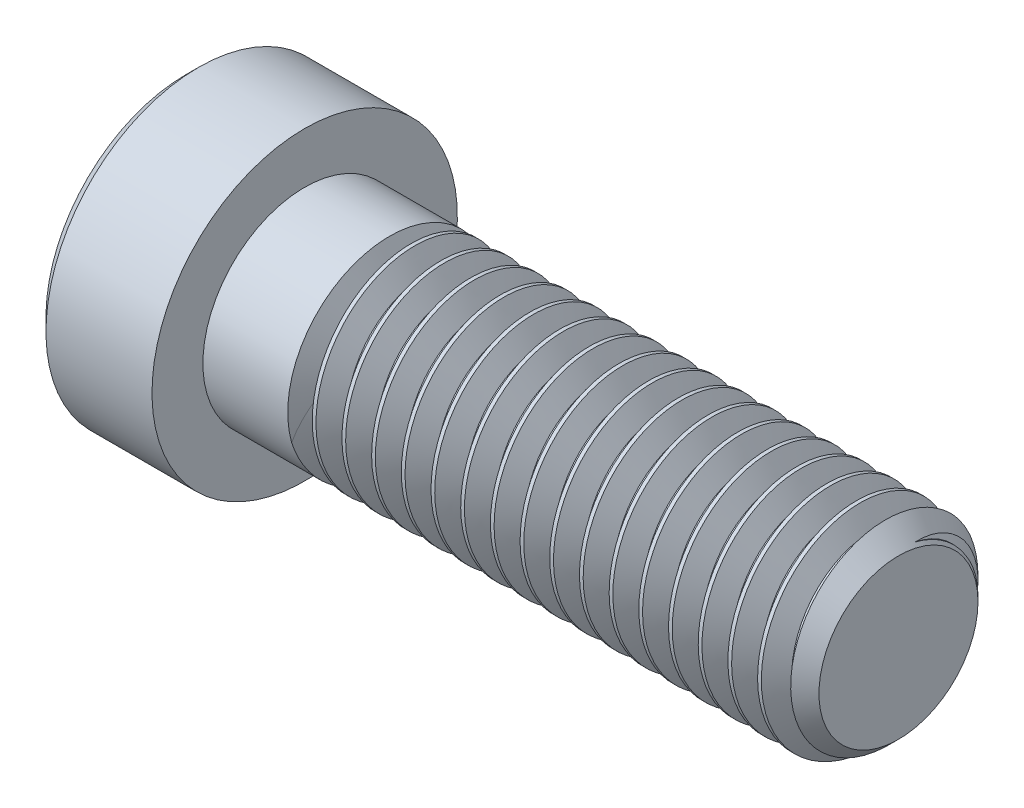
SolidWorks part; units mm, degrees
ref_plane "Front Plane" through (0, 0, 0) normal (0, 0, 1) x (1, 0, 0)
ref_plane "Top Plane" through (0, 0, 0) normal (0, 1, 0) x (1, 0, 0)
ref_plane "Right Plane" through (0, 0, 0) normal (1, 0, 0) x (0, 0, -1)
sketch "Sketch1" plane through (0, 0, 0) normal (0, 0, 1) x (1, 0, 0)
  line L0 (17.5, 0) -> (-17.5, 0) construction
  line L1 (17.5, 6) -> (17.5, -6) construction
  line L2 (-17.5, 9) -> (-17.5, -9) construction
  line L3 (-17.5, 9) -> (-23.75, 9) construction
  line L4 (-23.75, 9) -> (-24.5, 8.25) construction
  line L5 (-24.5, 8.25) -> (-24.5, -8.25) construction
  line L6 (-24.5, -8.25) -> (-23.75, -9) construction
  line L7 (-23.75, -9) -> (-17.5, -9) construction
  point P7 (-21, 0)
  point P12 (10.5, -6)
  dimension "D1" = 45
  dimension "Dec." = 12
  dimension "Length" = 35
  dimension "Head Dia" = 18
  dimension "Head Height" = 7
  dimension "Chamfer" = 0.75
  dimension "D2" = 7
  dimension "D3" = 3.5
ref_plane "Plane1" through (17.5, 0, 0) normal (1, 0, 0) x (0, 0, -1)
ref_plane "Plane2" through (-24.5, 0, 0) normal (1, 0, 0) x (0, 0, -1)
sketch "Sketch2" plane through (17.5, 0, 0) normal (1, 0, 0) x (0, 0, -1)
  circle A0 centre (0, 0) radius 6
extrude "Boss-Extrude1" add sketch "Sketch2" against normal up to vertex (35 mm away) up to point (-17.5, 0, 0)
sketch "Sketch3" plane through (17.5, 0, 0) normal (1, 0, 0) x (0, 0, -1)
  circle A0 centre (0, 0) radius 6 construction
  circle A1 centre (0, 0) radius 6
curve "Helix/Spiral1" pitch 1.75 height 36.75 radius 6 centre (17.5, 0, 0) axis (-1, 0, 0) start towards (0, 1, 0) parameters "Pitch"=1.75
chamfer "Chamfer1" distance 1.3125 angle 45 1 edges at (17.5, 0, -6)
sketch "Sketch5" plane through (0, 0, 0) normal (0, 0, 1) x (1, 0, 0)
  line L0 (16.7344, 6) -> (18.2656, 6)
  line L1 (18.2656, 6) -> (17.6094, 4.8633)
  line L2 (17.6094, 4.8633) -> (17.3906, 4.8633)
  line L3 (17.3906, 4.8633) -> (16.7344, 6)
  line L4 (17.5, 4.8633) -> (17.5, 6) construction
  line L5 (17.0625, 5.4317) -> (17.9375, 5.4317) construction
  dimension "D1" = 60
  dimension "D2" = 0.875
  dimension "D3" = 0.2188
sweep "Cut-Sweep1" cut profiles "Sketch5" path "Helix/Spiral1" align with end faces yes
sketch "Sketch4" plane through (-24.5, 0, 0) normal (1, 0, 0) x (0, 0, -1)
  line L0 (-9, 0.7937) -> (9, 0.7937) construction
  line L1 (0, 4.6188) -> (-4, 2.3094)
  line L2 (-4, 2.3094) -> (-4, -2.3094)
  line L3 (-4, -2.3094) -> (0, -4.6188)
  line L4 (0, -4.6188) -> (4, -2.3094)
  line L5 (4, -2.3094) -> (4, 2.3094)
  line L6 (4, 2.3094) -> (0, 4.6188)
  line L7 (0, 0) -> (0, 0.7937) construction
  circle A0 centre (0, 0) radius 4 construction
  dimension "Hex Size" = 8
  dimension "D1" = 18
  dimension "D2" = 0.7937
sketch "Sketch6" plane through (0, 0, 0) normal (0, 0, 1) x (1, 0, 0)
  line L0 (-23.75, 9) -> (-24.5, 8.25) construction
  line L1 (-17.5, 9) -> (-23.75, 9) construction
  line L2 (-17.5, 9) -> (-17.5, -9) construction
  line L3 (-24.5, 8.25) -> (-24.5, -8.25) construction
  line L4 (-23.75, 9) -> (-24.5, 8.25)
  line L5 (-17.5, 9) -> (-23.75, 9)
  line L6 (-17.5, 9) -> (-17.5, 0)
  line L7 (-24.5, 8.25) -> (-24.5, 0)
  line L8 (-17.5, 0) -> (-24.5, 0) construction
  line L9 (-17.5, 0) -> (-24.5, 0)
revolve "Revolve1" add sketch "Sketch6" angle 360 about L8
extrude "Cut-Extrude1" cut sketch "Sketch4" along normal up to vertex (3.5 mm away) up to point (-21, 0, 0)
sketch "Sketch8" plane through (-24.5, 0, 0) normal (-1, 0, 0) x (0, 0, 1)
  circle A1 centre (0, 0) radius 4.6188
extrude "Cut-Extrude2" cut sketch "Sketch8" against normal blind 1 draft 65
sketch "Sketch9" plane through (0, 0, 0) normal (0, 0, 1) x (1, 0, 0)
  line L0 (-17.5, 0) -> (-17.5, 6)
  line L1 (-17.5, -9) -> (-17.5, 9) construction
  line L2 (-17.5, 6) -> (-12.5, 6)
  line L3 (-12.5, 6) -> (-10.5491, 2)
  line L4 (-10.5491, 2) -> (-10.5491, 0)
  line L5 (-10.5491, 0) -> (-17.5, 0)
  line L6 (-12.5, 6) -> (-12.5, 4) construction
  line L7 (17.5, -4.6875) -> (17.5, 4.6875) construction
  line L8 (-12.5, 4) -> (-12.5, 2) construction
  line L9 (-12.5, 2) -> (-12.5, 0) construction
  line L11 (52.5, -6) -> (-17.5, -6) construction
  line L12 (52.5, -6) -> (52.5, 6) construction
  line L13 (52.5, 6) -> (-17.5, 6) construction
  line L14 (-17.5, -6) -> (-17.5, 6) construction
  line L15 (52.5, -6) -> (-17.5, 6) construction
  line L16 (52.5, 6) -> (-17.5, -6) construction
  point P5 (-12.3594, -6)
  point P8 (17.5, 0)
  point P21 (17.5, 6)
  dimension "D1" = 26
  dimension "Thread Min" = 30
revolve "Revolve2" add sketch "Sketch9" angle 360 mid plane about L5
equation "\"D3@Helix/Spiral1\" = \"Length@Sketch1\"+\"Pitch@Helix/Spiral1\""
equation "\"D3@Sketch5\" = \"Pitch@Helix/Spiral1\"*.125"
equation "\"D2@Sketch5\" = \"Pitch@Helix/Spiral1\"*.50"
equation "\"D1@Chamfer1\" = \"Pitch@Helix/Spiral1\"*.75"
equation "\"D2@Sketch1\" = \"Pitch@Helix/Spiral1\"*4"
equation "\"D1@Sketch4\" = \"Head Dia@Sketch1\""
equation "\"D3@Sketch1\" = \"Head Height@Sketch1\"/2"
